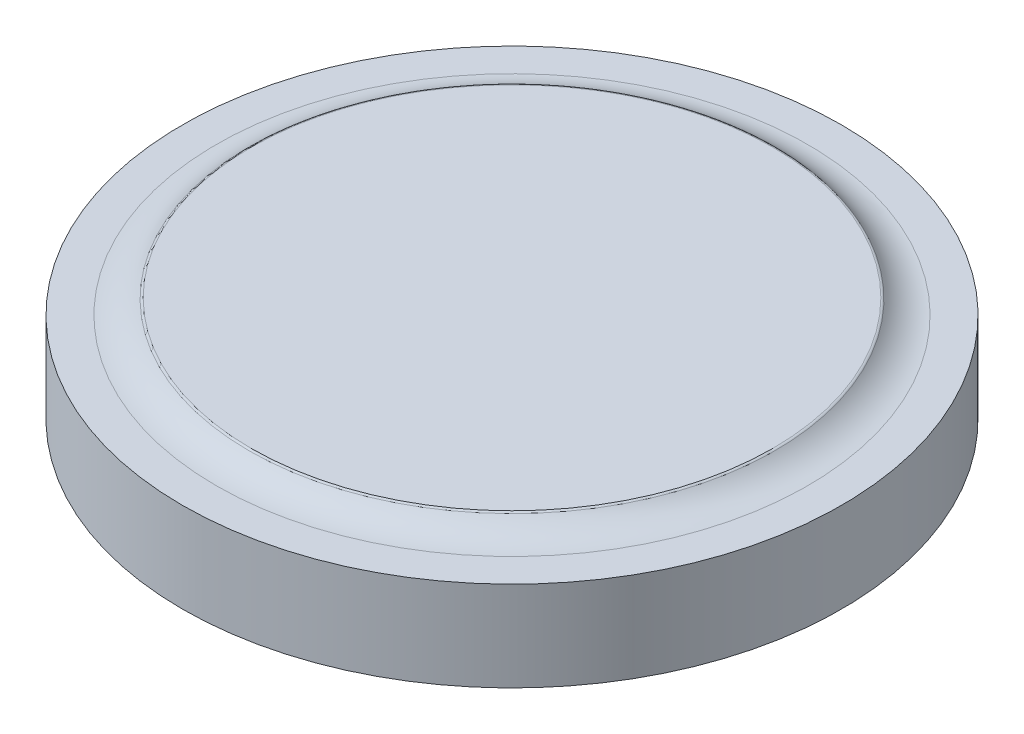
SolidWorks part; units mm, degrees
ref_plane "前视基准面" through (0, 0, 0) normal (0, 0, 1) x (1, 0, 0)
ref_plane "上视基准面" through (0, 0, 0) normal (0, 1, 0) x (1, 0, 0)
ref_plane "右视基准面" through (0, 0, 0) normal (1, 0, 0) x (0, 0, -1)
sketch "草图1" plane through (0, 0, 0) normal (0, 1, 0) x (1, 0, 0)
  circle A0 centre (0, 0) radius 11
  dimension "D1" = 22
extrude "凸台-拉伸1" add sketch "草图1" along normal blind 3
sketch "草图2" plane through (0, 3, 0) normal (0, 1, 0) x (1, 0, 0)
  circle A0 centre (0, 0) radius 8.75
  dimension "D1" = 17.5
extrude "凸台-拉伸2" add sketch "草图2" along normal blind 0.5
fillet "圆角1" radius 1.5 1 edges at (0, 3, 8.75)
fillet "圆角2" radius 0.1 1 edges at (0, 3.5, 8.75)
sketch "方向草图" plane through (0, 3, 0) normal (0, 1, 0) x (1, 0, 0)
  circle A0 centre (0, 0) radius 9.868 construction
  circle A1 centre (0, 0) radius 11 construction
  circle A2 centre (0, 0) radius 9.868
  circle A3 centre (0, 0) radius 11 construction
  point P5 (0, 0)
other "成形工具1"
